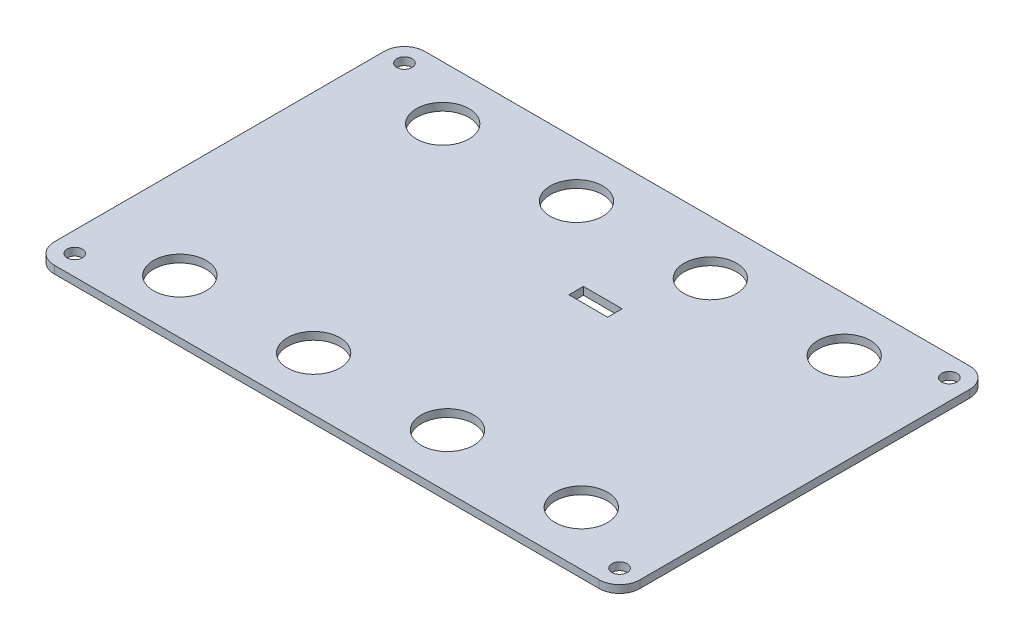
SolidWorks part; units mm, degrees
ref_plane "Front Plane" through (0, 0, 0) normal (0, 0, 1) x (1, 0, 0)
ref_plane "Top Plane" through (0, 0, 0) normal (0, 1, 0) x (1, 0, 0)
ref_plane "Right Plane" through (0, 0, 0) normal (1, 0, 0) x (0, 0, -1)
sketch "pcb" plane through (0, 0, 0) normal (0, 1, 0) x (1, 0, 0)
  line L0 (-14, -27.5) -> (-42, -27.5) construction
  line L1 (-57, -37.5) -> (57, -37.5)
  line L2 (-60, -34.5) -> (-60, 34.5)
  line L3 (-57, 37.5) -> (57, 37.5)
  line L4 (60, -34.5) -> (60, 34.5)
  line L5 (-60, -37.5) -> (60, 37.5) construction
  line L6 (-60, 37.5) -> (60, -37.5) construction
  line L7 (-14, -27.5) -> (14, -27.5) construction
  line L8 (14, -27.5) -> (42, -27.5) construction
  line L9 (-42, -27.5) -> (-60, -27.5) construction
  line L10 (42, -27.5) -> (60, -27.5) construction
  line L11 (-60, 0) -> (60, 0) construction
  line L13 (2.43, 12.5075) -> (10.05, 12.5075)
  line L14 (2.43, 12.5075) -> (2.43, 9.9675)
  line L15 (2.43, 9.9675) -> (10.05, 9.9675)
  line L16 (10.05, 12.5075) -> (10.05, 9.9675)
  arc A0 (-57, -37.5) -> (-60, -34.5) centre (-57, -34.5) cw
  arc A1 (57, -37.5) -> (60, -34.5) centre (57, -34.5) ccw
  arc A2 (57, 37.5) -> (60, 34.5) centre (57, 34.5) cw
  arc A3 (-60, 34.5) -> (-57, 37.5) centre (-57, 34.5) cw
  circle A4 centre (-57, 34.5) radius 1.6
  circle A5 centre (57, 34.5) radius 1.6
  circle A6 centre (57, -34.5) radius 1.6
  circle A7 centre (-57, -34.5) radius 1.6
  circle A8 centre (-42, -27.5) radius 5.5
  circle A9 centre (-14, -27.5) radius 5.5
  circle A10 centre (14, -27.5) radius 5.5
  circle A11 centre (42, -27.5) radius 5.5
  circle A12 centre (-42, 27.5) radius 5.5
  circle A13 centre (-14, 27.5) radius 5.5
  circle A14 centre (14, 27.5) radius 5.5
  circle A15 centre (42, 27.5) radius 5.5
  point P0 (0, 0)
  dimension "D3" = 3
  dimension "D4" = 3
  dimension "D5" = 3
  dimension "D6" = 3
  dimension "D7" = 3.2
  dimension "D9" = 11
  dimension "D10" = 18
  dimension "D1" = 120
  dimension "D2" = 75
  dimension "D8" = 10
  dimension "D11" = 62.43
  dimension "D12" = 47.4675
  dimension "D13" = 2.54
  dimension "D14" = 7.62
sketch "Sketch3" plane through (0, 0, 0) normal (0, 0, 1) x (1, 0, 0)
  line L0 (0, 0) -> (0, 1.6) construction
  line L1 (-57, 0) -> (57, 0) construction
  line L2 (0, 1.6) -> (0, 7) construction
  line L3 (0, 7) -> (0, 8.6) construction
  line L4 (0, 0) -> (0, -13.4) construction
  line L5 (0, -13.4) -> (0, -16.4) construction
  dimension "D1" = 1.6
  dimension "D2" = 3
  dimension "D3" = 13.4
  dimension "D4" = 5.4
  dimension "D5" = 1.6
  dimension "D6" = 25
sketch "Sketch2" plane through (0, 0, 0) normal (0, 1, 0) x (1, 0, 0)
  line L0 (-60, -34.5) -> (-60, 34.5) construction
  line L1 (-57, -37.5) -> (57, -37.5) construction
  line L2 (60, -34.5) -> (60, 34.5) construction
  line L3 (-57, 37.5) -> (57, 37.5) construction
  line L4 (-60, -34.5) -> (-60, 34.5)
  line L5 (-57, -37.5) -> (57, -37.5)
  line L6 (60, -34.5) -> (60, 34.5)
  line L7 (-57, 37.5) -> (57, 37.5)
  line L8 (-61.25, -34.5) -> (-61.25, 34.5)
  line L9 (-57, -38.75) -> (57, -38.75)
  line L10 (61.25, -34.5) -> (61.25, 34.5)
  line L11 (-57, 38.75) -> (57, 38.75)
  arc A0 (-57, 37.5) -> (-60, 34.5) centre (-57, 34.5) ccw construction
  arc A1 (-60, -34.5) -> (-57, -37.5) centre (-57, -34.5) ccw construction
  arc A2 (57, -37.5) -> (60, -34.5) centre (57, -34.5) ccw construction
  arc A3 (60, 34.5) -> (57, 37.5) centre (57, 34.5) ccw construction
  arc A4 (-57, 37.5) -> (-60, 34.5) centre (-57, 34.5) ccw
  arc A5 (-60, -34.5) -> (-57, -37.5) centre (-57, -34.5) ccw
  arc A6 (57, -37.5) -> (60, -34.5) centre (57, -34.5) ccw
  arc A7 (60, 34.5) -> (57, 37.5) centre (57, 34.5) ccw
  arc A8 (-57, 38.75) -> (-61.25, 34.5) centre (-57, 34.5) ccw
  arc A9 (-61.25, -34.5) -> (-57, -38.75) centre (-57, -34.5) ccw
  arc A10 (57, -38.75) -> (61.25, -34.5) centre (57, -34.5) ccw
  arc A11 (61.25, 34.5) -> (57, 38.75) centre (57, 34.5) ccw
  dimension "D1" = 1.25
extrude "Walls" add sketch "Sketch2" against normal up to vertex (13.4 mm away) and the other way up to vertex (7 mm away) up to point (0, -13.4, 0) other way up to point (0, 7, 0)
sketch "Sketch11" plane through (0, 0, 0) normal (0, 1, 0) x (1, 0, 0)
  line L0 (-60, -34.5) -> (-60, -31.5)
  line L1 (-60, -34.5) -> (-60, 34.5) construction
  line L2 (-60, -31.5) -> (-54, -31.5)
  line L3 (-54, -31.5) -> (-54, -37.5)
  line L4 (-57, -37.5) -> (57, -37.5) construction
  line L5 (-54, -37.5) -> (-57, -37.5)
  line L6 (-57, 37.5) -> (-54, 37.5)
  line L7 (-57, 37.5) -> (57, 37.5) construction
  line L8 (-54, 37.5) -> (-54, 31.5)
  line L9 (-54, 31.5) -> (-60, 31.5)
  line L10 (-60, 31.5) -> (-60, 34.5)
  line L11 (60, -31.5) -> (54, -31.5)
  line L12 (60, -34.5) -> (60, 34.5) construction
  line L13 (54, -31.5) -> (54, -37.5)
  line L14 (54, -37.5) -> (57, -37.5)
  line L15 (60, -31.5) -> (60, -34.5)
  line L16 (57, 37.5) -> (54, 37.5)
  line L17 (54, 37.5) -> (54, 31.5)
  line L18 (54, 31.5) -> (60, 31.5)
  line L19 (60, 31.5) -> (60, 34.5)
  arc A0 (-60, -34.5) -> (-57, -37.5) centre (-57, -34.5) ccw construction
  arc A1 (-60, -34.5) -> (-57, -37.5) centre (-57, -34.5) ccw
  arc A2 (-57, 37.5) -> (-60, 34.5) centre (-57, 34.5) ccw construction
  arc A3 (-57, 37.5) -> (-60, 34.5) centre (-57, 34.5) ccw
  circle A4 centre (-57, 34.5) radius 1.6 construction
  circle A5 centre (-57, 34.5) radius 1.6
  circle A6 centre (-57, -34.5) radius 1.6 construction
  circle A7 centre (-57, -34.5) radius 1.6
  arc A8 (57, -37.5) -> (60, -34.5) centre (57, -34.5) ccw construction
  arc A9 (57, -37.5) -> (60, -34.5) centre (57, -34.5) ccw
  circle A10 centre (57, -34.5) radius 1.6 construction
  circle A11 centre (57, -34.5) radius 1.6
  arc A12 (60, 34.5) -> (57, 37.5) centre (57, 34.5) ccw construction
  arc A13 (60, 34.5) -> (57, 37.5) centre (57, 34.5) ccw
  circle A14 centre (57, 34.5) radius 1.6 construction
  circle A15 centre (57, 34.5) radius 1.6
  dimension "D1" = 6
  dimension "D2" = 6
  dimension "D3" = 6
  dimension "D4" = 6
extrude "Boss-Extrude4" add sketch "Sketch11" against normal up to surface (13.4 mm away) up to face at (0, -13.4, 0)
fillet "Fillet1" radius 3 12 edges at (60, -6.7, -31.5) (54, -6.7, -37.5) (-54, -6.7, -37.5) (-60, -6.7, -31.5) (-54, -6.7, 37.5) (-60, -6.7, 31.5) (54, -6.7, 37.5) (60, -6.7, 31.5) (54, -6.7, 31.5) (-54, -6.7, 31.5) (-54, -6.7, -31.5) (54, -6.7, -31.5)
sketch "Sketch8" plane through (61.25, 0, 0) normal (1, 0, 0) x (0, 0, -1)
  line L0 (0, 1.6) -> (0, 7) construction
  line L1 (-3.17, 1.57) -> (3.17, 1.57)
  line L2 (-4.47, 2.87) -> (-4.47, 3.63)
  line L3 (-3.17, 4.93) -> (3.17, 4.93)
  line L4 (4.47, 2.87) -> (4.47, 3.63)
  line L5 (-4.47, 1.57) -> (4.47, 4.93) construction
  line L6 (-4.47, 4.93) -> (4.47, 1.57) construction
  line L8 (0, 0) -> (0, 1.6) construction
  line L9 (0, 0) -> (0, 1.6) construction
  line L11 (16.8, 1.6) -> (10.8, 1.6)
  line L12 (16.8, 1.6) -> (16.8, 6.82)
  line L13 (16.8, 6.82) -> (10.8, 6.82)
  line L14 (10.8, 1.6) -> (10.8, 6.82)
  line L15 (-37.5, 0) -> (37.5, 0) construction
  line L16 (0, 0) -> (0, -13.4) construction
  line L18 (23, 4.87) -> (26.6, 4.87)
  line L19 (23, 4.87) -> (23, 3.37)
  line L20 (23, 3.37) -> (26.6, 3.37)
  line L21 (26.6, 4.87) -> (26.6, 3.37)
  arc A0 (3.17, 4.93) -> (4.47, 3.63) centre (3.17, 3.63) cw
  arc A1 (3.17, 1.57) -> (4.47, 2.87) centre (3.17, 2.87) ccw
  arc A2 (-3.17, 1.57) -> (-4.47, 2.87) centre (-3.17, 2.87) cw
  arc A3 (-4.47, 3.63) -> (-3.17, 4.93) centre (-3.17, 3.63) cw
  circle A4 centre (-15.5, -6.55) radius 3.25
  point P0 (0, 3.25)
  point P10 (13.8, 1.6)
  dimension "D4" = 1.3
  dimension "D5" = 1.3
  dimension "D6" = 1.3
  dimension "D7" = 1.3
  dimension "D11" = 6.5
  dimension "D1" = 3.36
  dimension "D2" = 8.94
  dimension "D3" = 3.25
  dimension "D8" = 13.8
  dimension "D9" = 6
  dimension "D10" = 5.22
  dimension "D12" = 6.55
  dimension "D13" = 15.5
  dimension "D14" = 1.5
  dimension "D15" = 3.6
  dimension "D16" = 1.77
  dimension "D17" = 9.2
extrude "Cut-Extrude3" cut sketch "Sketch8" along direction (1, 0, 0) on the side against the normal up to surface (1.25 mm away) up to face at (60, -1.6, 0)
sketch "Sketch10" plane through (-61.25, 0, 0) normal (-1, 0, 0) x (0, 0, 1)
  line L0 (-34.5, 7) -> (34.5, 7) construction
  line L1 (5.84, 1.6) -> (26.16, 1.6)
  line L2 (5.84, 1.6) -> (5.84, 7)
  line L3 (5.84, 7) -> (26.16, 7)
  line L4 (26.16, 1.6) -> (26.16, 7)
  line L6 (-5.84, 1.6) -> (-26.16, 1.6)
  line L7 (-5.84, 1.6) -> (-5.84, 7)
  line L8 (-5.84, 7) -> (-26.16, 7)
  line L9 (-26.16, 1.6) -> (-26.16, 7)
  line L10 (0, 0) -> (0, 1.6) construction
  line L15 (0, 0) -> (0, 1.6) construction
  line L16 (-5.84, 1.6) -> (0, 1.6) construction
  line L17 (0, 1.6) -> (5.84, 1.6) construction
  line L22 (-1.8, 4.87) -> (1.8, 4.87)
  line L23 (-1.8, 4.87) -> (-1.8, 3.37)
  line L24 (-1.8, 3.37) -> (1.8, 3.37)
  line L25 (1.8, 4.87) -> (1.8, 3.37)
  point P10 (0, 3.37)
  dimension "D1" = 20.32
  dimension "D2" = 20.32
  dimension "D3" = 11.68
  dimension "D4" = 3.6
  dimension "D5" = 1.5
  dimension "D6" = 1.77
extrude "Cut-Extrude4" cut sketch "Sketch10" against normal up to next
other "Move Face3" flip direction yes face at (60.625, 4.12, -23) face at (60.625, 4.87, -24.8) face at (60.625, 4.12, -26.6) face at (60.625, 3.37, -24.8) offset 0.25 parameters "D1"=0.25
other "Move Face4" flip direction yes face at (60, -6.55, 12.25) face at (60.625, 2.0854, 3.9546) face at (60.625, 3.25, 4.47) face at (60.625, 4.4146, 3.9546) face at (60.625, 4.93, 0) face at (60.625, 2.0854, -3.9546) face at (60.625, 1.57, 0) face at (60.625, 3.25, -4.47) face at (60.625, 4.4146, -3.9546) face at (60.625, 1.6, -13.8) face at (60.625, 4.21, -16.8) face at (60.625, 4.21, -10.8) face at (60.625, 6.82, -13.8) offset 0.25 parameters "D1"=0.25
other "Move Face1" flip direction yes face at (-60.625, 4.3, 26.16) face at (-60.625, 1.6, 16) face at (-60.625, 4.3, 5.84) face at (-60.625, 4.3, -26.16) face at (-60.625, 1.6, -16) face at (-60.625, 4.3, -5.84) offset 1 parameters "D1"=1
other "Move Face2" flip direction yes face at (-60.625, 4.12, -1.8) face at (-60.625, 4.87, 0) face at (-60.625, 3.37, 0) face at (-60.625, 4.12, 1.8) offset 0.25 parameters "D1"=0.25
sketch "Sketch4" plane through (0, -13.4, 0) normal (0, -1, 0) x (1, 0, 0)
  line L4 (-57, -38.75) -> (57, -38.75)
  line L5 (61.25, -34.5) -> (61.25, 34.5)
  line L6 (57, 38.75) -> (-57, 38.75)
  line L7 (-61.25, 34.5) -> (-61.25, -34.5)
  line L8 (-57, -38.75) -> (57, -38.75)
  line L9 (61.25, -34.5) -> (61.25, 34.5)
  line L10 (57, 38.75) -> (-57, 38.75)
  line L11 (-61.25, 34.5) -> (-61.25, -34.5)
  circle A0 centre (57, -34.5) radius 2.15
  circle A1 centre (-57, -34.5) radius 2.15
  circle A2 centre (-57, 34.5) radius 2.15
  circle A3 centre (57, 34.5) radius 2.15
  arc A4 (-61.25, -34.5) -> (-57, -38.75) centre (-57, -34.5) ccw
  arc A5 (57, -38.75) -> (61.25, -34.5) centre (57, -34.5) ccw
  arc A6 (61.25, 34.5) -> (57, 38.75) centre (57, 34.5) ccw
  arc A7 (-57, 38.75) -> (-61.25, 34.5) centre (-57, 34.5) ccw
  arc A8 (-61.25, -34.5) -> (-57, -38.75) centre (-57, -34.5) ccw
  arc A9 (57, -38.75) -> (61.25, -34.5) centre (57, -34.5) ccw
  arc A10 (61.25, 34.5) -> (57, 38.75) centre (57, 34.5) ccw
  arc A11 (-57, 38.75) -> (-61.25, 34.5) centre (-57, 34.5) ccw
  dimension "D2" = 4.3
  dimension "D1" = 0
extrude "Bottom Lid" add sketch "Sketch4" along normal blind 3 separate body
sketch "Sketch5" plane through (0, 7, 0) normal (0, 1, 0) x (1, 0, 0)
  line L0 (2.43, 12.5075) -> (2.43, 9.9675) construction
  line L1 (2.43, 9.9675) -> (10.05, 9.9675) construction
  line L2 (2.43, 12.5075) -> (10.05, 12.5075) construction
  line L3 (10.05, 12.5075) -> (10.05, 9.9675) construction
  line L4 (57, 38.75) -> (-57, 38.75)
  line L5 (61.25, -34.5) -> (61.25, 34.5)
  line L6 (-57, -38.75) -> (57, -38.75)
  line L7 (-61.25, 34.5) -> (-61.25, -34.5)
  line L12 (57, 38.75) -> (-57, 38.75)
  line L13 (61.25, -34.5) -> (61.25, 34.5)
  line L14 (-57, -38.75) -> (57, -38.75)
  line L15 (-61.25, 34.5) -> (-61.25, -34.5)
  line L16 (2.43, 12.5075) -> (2.43, 9.9675)
  line L17 (2.43, 9.9675) -> (10.05, 9.9675)
  line L18 (2.43, 12.5075) -> (10.05, 12.5075)
  line L19 (10.05, 12.5075) -> (10.05, 9.9675)
  circle A3 centre (42, 27.5) radius 5.5 construction
  circle A15 centre (42, 27.5) radius 5.5
  circle A16 centre (-14, 27.5) radius 5.5 construction
  circle A17 centre (14, 27.5) radius 5.5 construction
  circle A18 centre (-14, 27.5) radius 5.5
  circle A19 centre (14, 27.5) radius 5.5
  circle A20 centre (-42, 27.5) radius 5.5 construction
  circle A21 centre (-42, 27.5) radius 5.5
  circle A22 centre (42, -27.5) radius 5.5 construction
  circle A23 centre (14, -27.5) radius 5.5 construction
  circle A24 centre (-14, -27.5) radius 5.5 construction
  circle A25 centre (-42, -27.5) radius 5.5 construction
  circle A26 centre (42, -27.5) radius 5.5
  circle A27 centre (14, -27.5) radius 5.5
  circle A28 centre (-14, -27.5) radius 5.5
  circle A29 centre (-42, -27.5) radius 5.5
  circle A30 centre (-57, -34.5) radius 1.6 construction
  circle A31 centre (-57, 34.5) radius 1.6 construction
  circle A32 centre (57, 34.5) radius 1.6 construction
  circle A33 centre (57, -34.5) radius 1.6 construction
  circle A34 centre (-57, -34.5) radius 1.6
  circle A35 centre (-57, 34.5) radius 1.6
  circle A36 centre (57, 34.5) radius 1.6
  circle A37 centre (57, -34.5) radius 1.6
  arc A38 (-57, 38.75) -> (-61.25, 34.5) centre (-57, 34.5) ccw
  arc A39 (61.25, 34.5) -> (57, 38.75) centre (57, 34.5) ccw
  arc A40 (57, -38.75) -> (61.25, -34.5) centre (57, -34.5) ccw
  arc A41 (-61.25, -34.5) -> (-57, -38.75) centre (-57, -34.5) ccw
  arc A42 (-57, 38.75) -> (-61.25, 34.5) centre (-57, 34.5) ccw
  arc A43 (61.25, 34.5) -> (57, 38.75) centre (57, 34.5) ccw
  arc A44 (57, -38.75) -> (61.25, -34.5) centre (57, -34.5) ccw
  arc A45 (-61.25, -34.5) -> (-57, -38.75) centre (-57, -34.5) ccw
  dimension "D1" = 0
extrude "Top Lid" add sketch "Sketch5" along normal blind 1.6 separate body
other "Move Face5" flip direction yes face at (2.43, 7.8, -11.2375) face at (6.24, 7.8, -9.9675) face at (10.05, 7.8, -11.2375) face at (6.24, 7.8, -12.5075) offset 0.25 parameters "D1"=0.25
delete or keep bodies "Body-Delete/Keep 1" [suppressed] type keep bodies bodies 120
delete or keep bodies "Body-Delete/Keep 2" type keep bodies bodies 124
delete or keep bodies "Body-Delete/Keep 3" [suppressed] type keep bodies bodies 102
equation "\"D2@Sketch10\"=\"D1@Sketch10\""
equation "\"D2@Sketch11\"=\"D1@Sketch11\""
equation "\"D3@Sketch11\"=\"D1@Sketch11\""
equation "\"D4@Sketch11\"=\"D1@Sketch11\""
